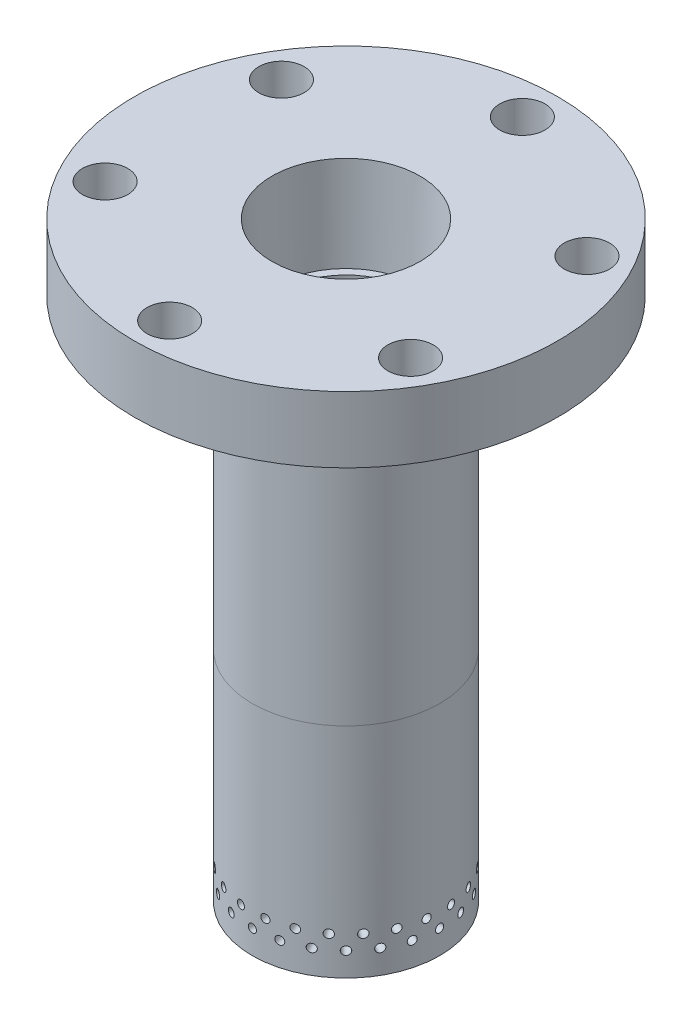
SolidWorks part; units mm, degrees
note: '?' marks a value the reader was unsure of.
material "AISI 304"
ref_plane "Front Plane" through (0, 0, 0) normal (0, 0, 1) x (1, 0, 0)
ref_plane "Top Plane" through (0, 0, 0) normal (0, 1, 0) x (1, 0, 0)
ref_plane "Right Plane" through (0, 0, 0) normal (1, 0, 0) x (0, 0, -1)
sketch "Sketch1" plane through (0, 0, 0) normal (0, 0, 1) x (1, 0, 0)
  line L0 (0, 0) -> (0, 17.7404) construction
  line L1 (0, 0) -> (-30.48, 0)
  line L2 (-30.48, 0) -> (-30.48, -9.525)
  line L3 (-30.48, -9.525) -> (-21, -9.525)
  line L4 (-13.5, -9.525) -> (-13.5, -90.246)
  line L5 (-13.5, -90.246) -> (0, -90.246)
  line L13 (-18, -9.525) -> (-18, -7.775)
  line L14 (-18, -7.775) -> (-21, -7.775)
  line L15 (-21, -7.775) -> (-21, -9.525)
  line L16 (-18, -9.525) -> (-13.5, -9.525)
  line L18 (0, -90.246) -> (0, 0)
  line L19 (-13.5, -53.721) -> (13.5, -53.721) construction
  line L20 (-6.75, -53.721) -> (-6.75, -80.721) construction
  line L21 (-13.5, -80.721) -> (0, -80.721) construction
  point P7 (0, -53.721)
  point P21 (-6.75, -80.721)
  dimension "D1" = 60.96
  dimension "D2" = 27
  dimension "D3" = 9.525
  dimension "D4" = 44.196
  dimension "D5" = 9.525
  dimension "D12" = 1.75
  dimension "D13" = 36
  dimension "D14" = 42
revolve "Revolve1" add sketch "Sketch1" angle 360 about L0
hole_wizard "1/2 NPT Tapped Hole1" positions "Sketch2" profile "Sketch3" size "1/2" standard "ANSI Inch"
sketch "Sketch2" plane through (0, 0, 0) normal (0, 1, 0) x (1, 0, 0)
  point P0 (0, 0)
sketch "Sketch3" plane through (0, 0, 0) normal (1, 0, 0) x (0, 0, 1)
  line L0 (0, 0) -> (0, 86.331)
  line L1 (9.1281, 82.55) -> (0, 86.331)
  line L2 (-9.1281, 82.55) -> (0, 86.331) construction
  line L3 (9.1281, 82.55) -> (9.1281, 13.462)
  line L4 (9.1281, 13.462) -> (10.2617, 13.462)
  line L5 (10.2617, 13.462) -> (10.6647, 0)
  line L6 (-10.2617, 13.462) -> (-10.6647, 0) construction
  line L7 (10.6647, 0) -> (0, 0)
  line L8 (0, -6.35) -> (0, 107.95) construction
  line L11 (-9.1281, 13.462) -> (-10.2617, 13.462) construction
  dimension "Tap Drill Dia." = 18.2562
  dimension "Tap Drill Depth" = 82.55
  dimension "Thread Dia." = 21.3295
  dimension "Thread Angle" = 3.43
  dimension "Thread Depth" = 13.462
  dimension "Drill Angle" = 135
hole_wizard "3/8 NPT Tapped Hole1" [suppressed] positions "Sketch9" profile "Sketch10" size "3/8" standard "ANSI Inch"
sketch "Sketch9" plane through (0, 0, 0) normal (0, 1, 0) x (1, 0, 0)
  point P0 (0, 0)
sketch "Sketch10" plane through (0, 0, 0) normal (1, 0, 0) x (0, 0, 1)
  line L0 (0, 0) -> (0, 85.5064)
  line L1 (7.1374, 82.55) -> (0, 85.5064)
  line L2 (-7.1374, 82.55) -> (0, 85.5064) construction
  line L3 (7.1374, 82.55) -> (7.1374, 10.414)
  line L4 (7.1374, 10.414) -> (8.2632, 10.414)
  line L5 (8.2632, 10.414) -> (8.575, 0)
  line L6 (-8.2632, 10.414) -> (-8.575, 0) construction
  line L7 (8.575, 0) -> (0, 0)
  line L8 (0, -6.35) -> (0, 107.95) construction
  line L11 (-7.1374, 10.414) -> (-8.2632, 10.414) construction
  dimension "Tap Drill Dia." = 14.2748
  dimension "Tap Drill Depth" = 82.55
  dimension "Thread Dia." = 17.15
  dimension "Thread Angle" = 3.43
  dimension "Thread Depth" = 10.414
  dimension "Drill Angle" = 135
hole_wizard "1/4 Clearance Hole1" positions "Sketch4" profile "Sketch5" hole size "1/4" standard "ANSI Inch"
sketch "Sketch4" plane through (0, 0, 0) normal (0, 1, 0) x (1, 0, 0)
  line L1 (0, 25.4) -> (-21.997, 12.7)
  line L2 (-21.997, 12.7) -> (-21.997, -12.7)
  line L3 (-21.997, -12.7) -> (0, -25.4)
  line L4 (0, -25.4) -> (21.997, -12.7)
  line L5 (21.997, -12.7) -> (21.997, 12.7)
  line L6 (21.997, 12.7) -> (0, 25.4)
  circle A0 centre (0, 0) radius 25.4 construction
  point P3 (0, 25.4)
  point P4 (-21.997, 12.7)
  point P5 (-21.997, -12.7)
  point P6 (0, -25.4)
  point P7 (21.997, -12.7)
  point P8 (21.997, 12.7)
  dimension "D1" = 50.8
sketch "Sketch5" plane through (21.997, 0, -12.7) normal (1, 0, 0) x (0, 0, 1)
  line L0 (0, 0) -> (0, 24.5671)
  line L1 (0, 24.5671) -> (3.2639, 22.606)
  line L2 (3.2639, 22.606) -> (3.2639, 0)
  line L5 (3.2639, 0) -> (0, 0)
  line L10 (0, 24.5671) -> (-3.2639, 22.606) construction
  line L11 (0, -6.35) -> (0, 107.95) construction
  dimension "Hole Dia." = 6.5278
  dimension "Hole Depth" = 22.606
  dimension "Drill Angle" = 118
chamfer "Chamfer1" distance 1 angle 45 1 edges at (0, -9.525, -13.5)
other "CHANGE-LENGTH" [suppressed] parameters "D1"=15
chamfer "135-deg" distance 5.08 angle 67.5 1 edges at (0, -90.246, -13.5) first distance on face at (0, -10.525, 13.5)
sketch "Sketch12" plane through (0, 0, 0) normal (0, 0, 1) x (1, 0, 0)
  line L0 (-13.5, -53.721) -> (13.5, -53.721)
  line L1 (-13.5, -10.525) -> (-13.5, -85.166) construction
  line L2 (13.5, -85.166) -> (13.5, -10.525) construction
  line L3 (-30.48, -9.525) -> (30.48, -9.525) construction
  dimension "D1" = 44.196
split line "Split Line1"
sketch "Sketch13" plane through (0, 0, 0) normal (0, 0, 1) x (1, 0, 0)
  line L0 (-13.5, -80.721) -> (13.5, -80.721)
  line L1 (-13.5, -53.721) -> (-13.5, -85.166) construction
  line L2 (13.5, -85.166) -> (13.5, -53.721) construction
  line L3 (-13.5, -80.721) -> (-13.5, -53.721) construction
  line L4 (-13.5, -53.721) -> (13.5, -53.721) construction
sketch "Sketch6" plane through (0, 0, 0) normal (0, 0, 1) x (1, 0, 0)
  line L2 (0, -81.737) -> (0, 0) construction
  line L3 (-13.5, -80.721) -> (13.5, -80.721) construction
  circle A0 centre (0, -81.737) radius 0.5906
  dimension "D1" = 1.1811
  dimension "D2" = 1.016
extrude "#56" cut sketch "Sketch6" against normal through all
pattern_circular "CirPattern1" count 24 over 360 about axis through (0, 0, 0) along (0, -1, 0) of "#56"
ref_axis "Axis1" through (0, 4.5123, 0) along (0, -1, 0)?
ref_plane "Plane1" through (0, 0, 0) normal (0.9914, 0, 0.1305) x (0, -1, 0)
sketch "Sketch7" plane through (0, 0, 0) normal (0.9914, 0, 0.1305) x (0, -1, 0)
  line L0 (-4.5123, 0) -> (94.7583, 0) construction
  line L4 (80.721, -1.7621) -> (80.721, 1.7621) construction
  circle A0 centre (79.705, 0) radius 0.5905
  dimension "D1" = 1.1811
  dimension "D2" = 1.016
extrude "#56-2" cut sketch "Sketch7" against normal through all
pattern_circular "CirPattern2" count 24 over 360 about axis through (0, 0, 0) along (0, -1, 0) of "#56-2"
other "pipe-tap-geometry" [suppressed] parameters "D1"=1.3462
sketch "Sketch8" [suppressed] plane through (0, 0, 0) normal (0, 0, 1) x (1, 0, 0)
  line L0 (-5.0455, -69.525) -> (5.0455, -69.525) construction
  line L1 (8.9281, -60.946) -> (-8.9281, -60.946) construction
  line L2 (-8.9281, -60.946) -> (-3.5241, -66.35)
  line L3 (-3.5241, -66.35) -> (0, -66.35)
  line L4 (0, -66.35) -> (0, 0) construction
  line L5 (-8.9281, -60.946) -> (0, -60.946)
  line L6 (0, -66.35) -> (0, -60.946)
  dimension "D1" = 45
  dimension "D2" = 3.175
revolve "Cut-Revolve1" [suppressed] cut sketch "Sketch8" angle 360 about L4
sketch "Sketch11" plane through (0, -90.246, 0) normal (0, -1, 0) x (1, 0, 0)
  circle A1 centre (0, 0) radius 1.2358
  circle A3 centre (0, 0) radius 1.2358
  dimension "D1" = 0
extrude "Boss-Extrude1" [suppressed] add sketch "Sketch11" against normal up to surface (56.063 mm away) separate body
combine bodies "Combine1" [suppressed] operation type? add bodies to combine 113 108
